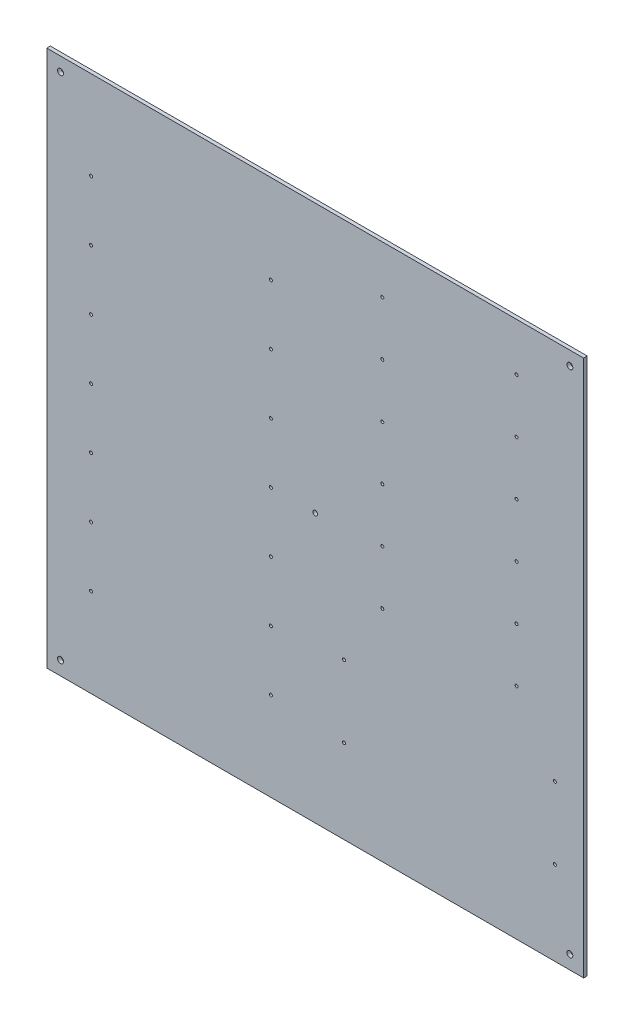
SolidWorks part; units mm, degrees
material "6061-T6 (SS)"
ref_plane "Piano frontale" through (0, 0, 0) normal (0, 0, 1) x (1, 0, 0)
ref_plane "Piano superiore" through (0, 0, 0) normal (0, 1, 0) x (1, 0, 0)
ref_plane "Piano destro" through (0, 0, 0) normal (1, 0, 0) x (0, 0, -1)
sketch "Schizzo1" plane through (0, 0, 0) normal (0, 0, 1) x (1, 0, 0)
  line L0 (0, 224) -> (448, 224) construction
  line L1 (0, 0) -> (448, 0)
  line L2 (0, 0) -> (0, 448)
  line L3 (0, 448) -> (448, 448)
  line L4 (448, 0) -> (448, 448)
  line L5 (224, 448) -> (224, 0) construction
  line L10 (0, 448) -> (0, 224) construction
  line L11 (0, 448) -> (0, 224) construction
  circle A0 centre (11.5, 436.5) radius 2.5
  circle A1 centre (436.5, 436.5) radius 2.5
  circle A2 centre (11.5, 11.5) radius 2.5
  circle A3 centre (436.5, 11.5) radius 2.5
  circle A4 centre (280, 183) radius 1.25
  circle A5 centre (392, 183) radius 1.25
  circle A7 centre (36.9588, 224) radius 1.25
  circle A9 centre (36.9588, 274) radius 1.25
  circle A10 centre (187.0412, 274) radius 1.25
  circle A11 centre (36.9588, 324) radius 1.25
  circle A12 centre (187.0412, 324) radius 1.25
  circle A13 centre (36.9588, 374) radius 1.25
  circle A14 centre (187.0412, 374) radius 1.25
  circle A15 centre (36.9588, 174) radius 1.25
  circle A16 centre (248, 70) radius 1.25
  circle A17 centre (248, 130) radius 1.25
  circle A18 centre (424, 130) radius 1.25
  circle A19 centre (424, 70) radius 1.25
  circle A20 centre (187.0412, 174) radius 1.25
  circle A21 centre (280, 408) radius 1.25
  circle A22 centre (392, 408) radius 1.25
  circle A23 centre (36.9588, 124) radius 1.25
  circle A24 centre (187.0412, 124) radius 1.25
  circle A25 centre (280, 363) radius 1.25
  circle A26 centre (392, 363) radius 1.25
  circle A27 centre (36.9588, 74) radius 1.25
  circle A28 centre (187.0412, 74) radius 1.25
  circle A29 centre (280, 318) radius 1.25
  circle A30 centre (392, 318) radius 1.25
  circle A33 centre (280, 273) radius 1.25
  circle A34 centre (392, 273) radius 1.25
  circle A37 centre (280, 228) radius 1.25
  circle A38 centre (392, 228) radius 1.25
  circle A69 centre (187.0412, 224) radius 1.25
  circle A70 centre (224, 224) radius 2
  point P33 (36.9588, 224)
  point P36 (36.9588, 174)
  point P37 (36.9588, 274)
  point P42 (36.9588, 324)
  point P53 (36.9588, 374)
  point P64 (36.9588, 124)
  point P71 (36.9588, 74)
  point P82 (253.9707, 256)
  point P89 (253.9707, 224)
  point P96 (253.9707, 192)
  point P103 (253.9707, 384)
  point P110 (253.9707, 352)
  point P117 (253.9707, 320)
  point P141 (253.9707, 288)
  point P148 (253.9707, 160)
  point P155 (253.9707, 128)
  point P162 (253.9707, 96)
  point P169 (253.9707, 64)
  point P179 (280.1758, 232.4048)
  point P193 (280.1085, 282.4047)
  point P207 (280.0413, 332.4047)
  dimension "D5" = 11.5
  dimension "D18" = 6
  dimension "D10" = 4
  dimension "D3" = 5
  dimension "D1" = 448
  dimension "D2" = 448
  dimension "D4" = 11.5
  dimension "D6" = 4
extrude "Estrusione-Estrusione1" add sketch "Schizzo1" against normal blind 3
